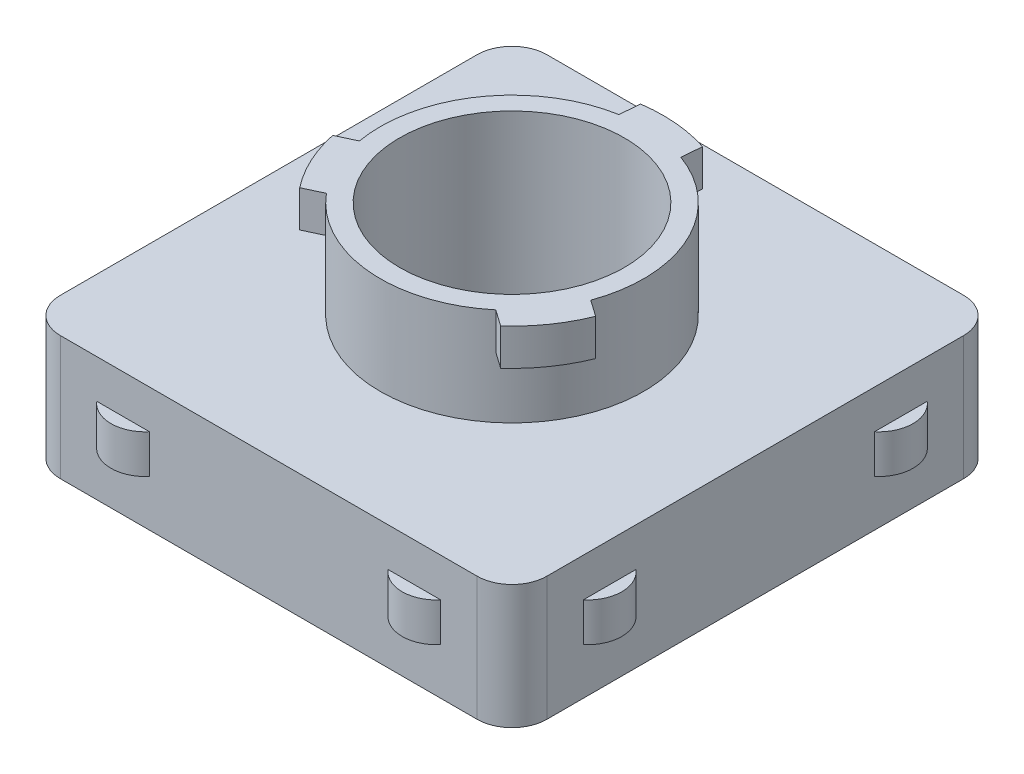
SolidWorks part; units mm, degrees
ref_plane "Front Plane" through (0, 0, 0) normal (0, 0, 1) x (1, 0, 0)
ref_plane "Top Plane" through (0, 0, 0) normal (0, 1, 0) x (1, 0, 0)
ref_plane "Right Plane" through (0, 0, 0) normal (1, 0, 0) x (0, 0, -1)
sketch "Sketch1" plane through (0, 0, 0) normal (0, 1, 0) x (1, 0, 0)
  line L1 (-19.9328, -19.9328) -> (19.9327, -19.9328)
  line L2 (-19.9328, -19.9328) -> (-19.9328, 19.9327)
  line L3 (-19.9328, 19.9327) -> (19.9327, 19.9327)
  line L4 (19.9327, -19.9328) -> (19.9327, 19.9327)
  line L5 (-19.9328, -19.9328) -> (19.9327, 19.9327) construction
  line L6 (-19.9328, 19.9327) -> (19.9327, -19.9328) construction
  point P0 (0, 0)
  dimension "D1" = 39.8655
extrude "Boss-Extrude1" add sketch "Sketch1" along normal blind 10.16
sketch "Sketch2" plane through (0, 10.16, 0) normal (0, 1, 0) x (1, 0, 0)
  line L4 (19.9327, -19.9328) -> (19.9327, 19.9327)
  line L5 (19.9327, 19.9327) -> (-19.9328, 19.9327)
  line L6 (-19.9328, 19.9327) -> (-19.9328, -19.9328)
  line L7 (-19.9328, -19.9328) -> (19.9327, -19.9328)
  line L8 (19.9327, -19.9328) -> (19.9327, 19.9327)
  line L9 (19.9327, 19.9327) -> (-19.9328, 19.9327)
  line L10 (-19.9328, 19.9327) -> (-19.9328, -19.9328)
  line L11 (-19.9328, -19.9328) -> (19.9327, -19.9328)
  circle A0 centre (0, 0) radius 10.795
  circle A1 centre (0, 0) radius 9.2075
  point P7 (0, 8.0979)
  dimension "D2" = 21.59
  dimension "D3" = 18.415
  dimension "D1" = 0
extrude "Boss-Extrude2" add sketch "Sketch2" along normal blind 8 contours A0 A1 region at (-10.4897, 10.16, 0)
sketch "Sketch5" plane through (0, 18.16, 0) normal (0, 1, 0) x (1, 0, 0)
  line L0 (2.794, -12.072) -> (2.794, -10.4272)
  line L1 (-2.794, -12.072) -> (-2.794, -10.4272)
  line L2 (0, 0) -> (10.1502, -7.1072) construction
  line L3 (0, 0) -> (0, -12.3911) construction
  line L4 (8.2862, -9.2129) -> (6.9389, -8.2695)
  line L5 (11.4914, -4.6355) -> (10.144, -3.6921)
  circle A0 centre (0, 0) radius 10.795 construction
  circle A1 centre (0, 0) radius 10.795
  arc A2 (2.794, -12.072) -> (-2.794, -12.072) centre (0, 0) cw
  arc A3 (8.2862, -9.2129) -> (11.4914, -4.6355) centre (0, 0) ccw
  point P5 (0, -12.3911)
  circle M5 centre (0, 0) radius 10.795
  dimension "D1" = 12.3911
  dimension "D2" = 5.588
  dimension "D3" = 55
  dimension "D4" = 5.588
extrude "Boss-Extrude3" add sketch "Sketch5" against normal blind 3 contours L4 A3 L5 M5 region at (9.4025, 18.16, 6.5837)
pattern_circular "CirPattern1" count 3 over 360 about axis through (0, 18.16, 0) along (0, 1, 0) of "Boss-Extrude3"
sketch "Sketch6" plane through (0, 10.16, 0) normal (0, 1, 0) x (1, 0, 0)
  line L0 (19.9327, 19.9327) -> (-19.9328, 19.9327) construction
  line L2 (19.9327, 19.9327) -> (-19.9328, 19.9327)
  line L5 (-14.0918, 20.9327) -> (-9.7737, 20.9327) construction
  line L6 (-19.9328, 19.9327) -> (-19.9328, -19.9328) construction
  line L8 (-14.0918, 19.9327) -> (-9.7737, 19.9327)
  line L9 (9.7737, 20.9327) -> (14.0917, 20.9327) construction
  line L10 (19.9327, -19.9328) -> (19.9327, 19.9327) construction
  arc A1 (-14.0918, 19.9327) -> (-9.7737, 19.9327) centre (-11.9328, 18.1021) cw
  arc A2 (9.7737, 19.9327) -> (14.0917, 19.9327) centre (11.9327, 18.1021) cw
  point P4 (0, 0)
  point P12 (0, 0)
  point P13 (0, 0)
  point P21 (0, 0)
  point P22 (0, 0)
  dimension "D1" = 1
  dimension "D2" = 8
  dimension "D3" = 1.8306
  dimension "D4" = 8
extrude "Boss-Extrude4" add sketch "Sketch6" against normal blind 6.35 contours A1 L2 | A2 L2 region at (-11.9328, 10.16, -20.3395) region at (11.9327, 10.16, -20.3395)
sketch "Sketch7" plane through (0, 10.16, 0) normal (0, 1, 0) x (1, 0, 0)
  line L0 (-9.7737, 19.9327) -> (-14.0918, 19.9327) construction
  line L2 (-9.7737, 19.9327) -> (-14.0918, 19.9327)
  line L4 (9.7737, 19.9327) -> (14.0917, 19.9327)
  line L10 (19.9327, -19.9328) -> (19.9327, 19.9327)
  line L11 (19.9327, 19.9327) -> (14.0917, 19.9327)
  line L12 (9.7737, 19.9327) -> (-9.7737, 19.9327)
  line L13 (-14.0918, 19.9327) -> (-19.9328, 19.9327)
  line L14 (-19.9328, 19.9327) -> (-19.9328, -19.9328)
  line L15 (-19.9328, -19.9328) -> (19.9327, -19.9328)
  line L16 (19.9327, -19.9328) -> (19.9327, 19.9327)
  line L17 (19.9327, 19.9327) -> (14.0917, 19.9327)
  line L18 (9.7737, 19.9327) -> (-9.7737, 19.9327)
  line L19 (-14.0918, 19.9327) -> (-19.9328, 19.9327)
  line L20 (-19.9328, 19.9327) -> (-19.9328, -19.9328)
  line L21 (-19.9328, -19.9328) -> (19.9327, -19.9328)
  arc A0 (-9.7737, 19.9327) -> (-14.0918, 19.9327) centre (-11.9328, 18.1021) ccw construction
  arc A2 (-9.7737, 19.9327) -> (-14.0918, 19.9327) centre (-11.9328, 18.1021) ccw
  arc A6 (14.0917, 19.9327) -> (9.7737, 19.9327) centre (11.9327, 18.1021) ccw
  arc A7 (-9.7737, 19.9327) -> (-14.0918, 19.9327) centre (-11.9328, 18.1021) ccw
  arc A8 (14.0917, 19.9327) -> (9.7737, 19.9327) centre (11.9327, 18.1021) ccw
  arc A9 (-9.7737, 19.9327) -> (-14.0918, 19.9327) centre (-11.9328, 18.1021) ccw
  arc M4 (-9.7737, 19.9327) -> (-14.0918, 19.9327) centre (-11.9328, 18.1021) ccw
  arc M19 (14.0917, 19.9327) -> (9.7737, 19.9327) centre (11.9327, 18.1021) ccw
  dimension "D1" = 0
extrude "Cut-Extrude1" cut sketch "Sketch7" against normal blind 3.175 contours L2 M4 | L4 M19 region at (-11.9328, 10.16, -20.3395) region at (11.9327, 10.16, -20.3395)
fillet "Fillet1" radius 2.8575 4 edges at (-19.9328, 5.08, 19.9328) (-19.9328, 5.08, -19.9327) (19.9327, 5.08, -19.9327) (19.9327, 5.08, 19.9328)
sketch "Sketch12" plane through (0, 0, 0) normal (0, 0, 1) x (1, 0, 0)
  line L0 (0, 0) -> (0, 19.1869) construction
sketch "Sketch13" plane through (0, 10.16, 0) normal (0, 1, 0) x (1, 0, 0)
  circle A0 centre (0, 0) radius 9.2075 construction
  circle A1 centre (0, 0) radius 9.2075
extrude "Cut-Extrude2" cut sketch "Sketch13" against normal through all
pattern_circular "CirPattern2" count 4 over 360 about axis through (0, 18.16, 0) along (0, 1, 0) of "Boss-Extrude4", "Cut-Extrude1"
